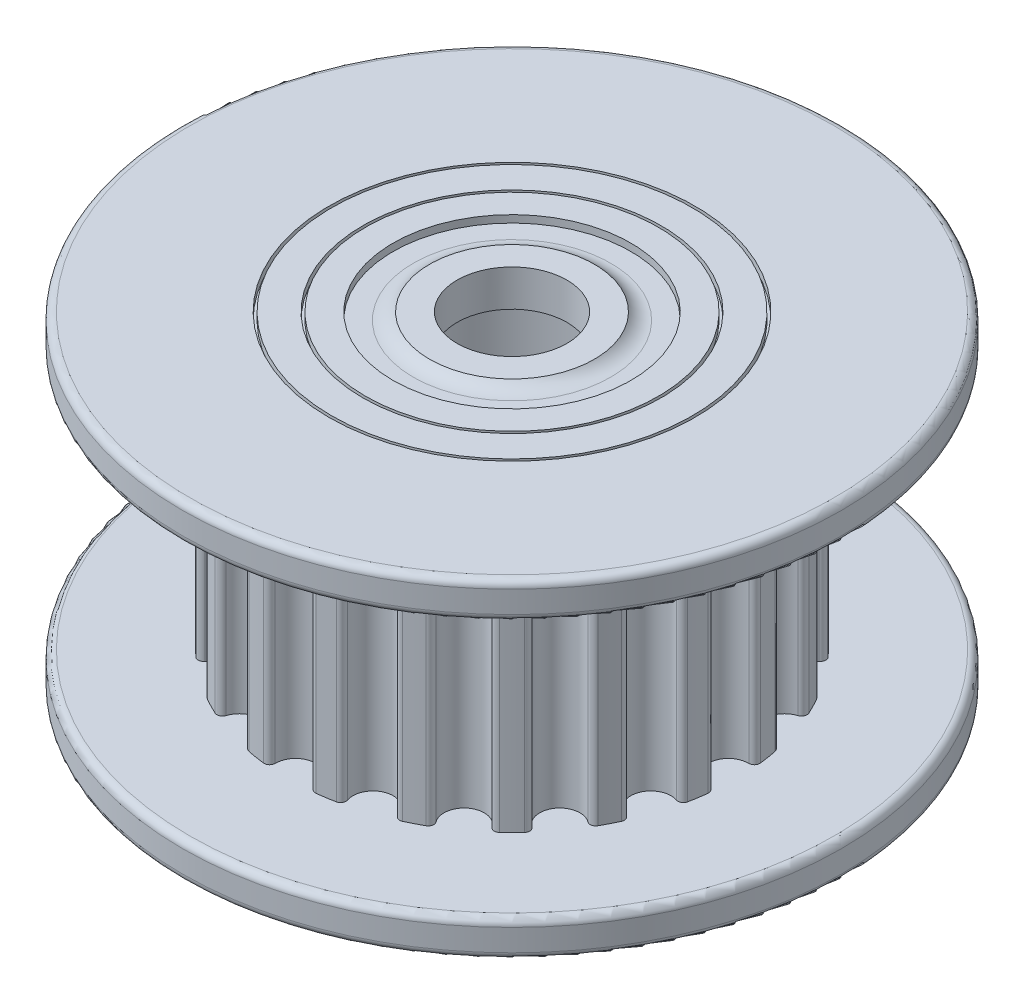
SolidWorks part; units mm, degrees
note: '?' marks a value the reader was unsure of.
material "1060 Alloy"
ref_plane "Спереди" through (0, 0, 0) normal (0, 0, 1) x (1, 0, 0)
ref_plane "Сверху" through (0, 0, 0) normal (0, 1, 0) x (1, 0, 0)
ref_plane "Справа" through (0, 0, 0) normal (1, 0, 0) x (0, 0, -1)
other "Configuration Table"
sketch "Эскиз1" plane through (0, 0, 0) normal (0, 1, 0) x (1, 0, 0)
  circle A0 centre (0, 0) radius 8
  circle A1 centre (0, 0) radius 2.5
  dimension "D1" = 16
  dimension "D2" = 5
extrude "Бобышка-Вытянуть1" add sketch "Эскиз1" along normal blind 7.45
sketch "Эскиз2" plane through (0, 7.45, 0) normal (0, 1, 0) x (1, 0, 0)
  arc A0 (-2.5575, 5.549) -> (-2.986, 5.3307) centre (0, 0) ccw
  circle A1 centre (0, 0) radius 2.5 construction
  circle A2 centre (0, 0) radius 2.5
  arc A3 (-0.55, 5.9169) -> (0.55, 5.9169) centre (0, 5.91) ccw
  arc A4 (1.3054, 5.7972) -> (2.3515, 5.4573) centre (1.8263, 5.6207) ccw
  arc A5 (3.0329, 5.1101) -> (3.9228, 4.4636) centre (3.4738, 4.7813) ccw
  arc A6 (4.4636, 3.9228) -> (5.1101, 3.0329) centre (4.7813, 3.4738) ccw
  arc A7 (5.4573, 2.3515) -> (5.7972, 1.3054) centre (5.6207, 1.8263) ccw
  arc A8 (5.9169, 0.55) -> (5.9169, -0.55) centre (5.91, 0) ccw
  arc A9 (5.7972, -1.3054) -> (5.4573, -2.3515) centre (5.6207, -1.8263) ccw
  arc A10 (5.1101, -3.0329) -> (4.4636, -3.9228) centre (4.7813, -3.4738) ccw
  arc A11 (3.9228, -4.4636) -> (3.0329, -5.1101) centre (3.4738, -4.7813) ccw
  arc A12 (2.3515, -5.4573) -> (1.3054, -5.7972) centre (1.8263, -5.6207) ccw
  arc A13 (0.55, -5.9169) -> (-0.55, -5.9169) centre (0, -5.91) ccw
  arc A14 (-1.3054, -5.7972) -> (-2.3515, -5.4573) centre (-1.8263, -5.6207) ccw
  arc A15 (-3.0329, -5.1101) -> (-3.9228, -4.4636) centre (-3.4738, -4.7813) ccw
  arc A16 (-4.4636, -3.9228) -> (-5.1101, -3.0329) centre (-4.7813, -3.4738) ccw
  arc A17 (-5.4573, -2.3515) -> (-5.7972, -1.3054) centre (-5.6207, -1.8263) ccw
  arc A18 (-5.9169, -0.55) -> (-5.9169, 0.55) centre (-5.91, 0) ccw
  arc A19 (-5.7972, 1.3054) -> (-5.4573, 2.3515) centre (-5.6207, 1.8263) ccw
  arc A20 (-5.1101, 3.0329) -> (-4.4636, 3.9228) centre (-4.7813, 3.4738) ccw
  arc A21 (-3.9228, 4.4636) -> (-3.0329, 5.1101) centre (-3.4738, 4.7813) ccw
  arc A22 (-2.3515, 5.4573) -> (-1.3054, 5.7972) centre (-1.8263, 5.6207) ccw
  arc A23 (-4.147, 4.4871) -> (-4.4871, 4.147) centre (0, 0) ccw
  arc A24 (-0.7176, 6.0677) -> (-1.1926, 5.9925) centre (0, 0) ccw
  arc A25 (1.1926, 5.9925) -> (0.7176, 6.0677) centre (0, 0) ccw
  arc A26 (2.986, 5.3307) -> (2.5575, 5.549) centre (0, 0) ccw
  arc A27 (4.4871, 4.147) -> (4.147, 4.4871) centre (0, 0) ccw
  arc A28 (5.549, 2.5575) -> (5.3307, 2.986) centre (0, 0) ccw
  arc A29 (6.0677, 0.7176) -> (5.9925, 1.1926) centre (0, 0) ccw
  arc A30 (-5.3307, 2.986) -> (-5.549, 2.5575) centre (0, 0) ccw
  arc A31 (-5.9925, 1.1926) -> (-6.0677, 0.7176) centre (0, 0) ccw
  arc A32 (-6.0677, -0.7176) -> (-5.9925, -1.1926) centre (0, 0) ccw
  arc A33 (-5.549, -2.5575) -> (-5.3307, -2.986) centre (0, 0) ccw
  arc A34 (-4.4871, -4.147) -> (-4.147, -4.4871) centre (0, 0) ccw
  arc A35 (-2.986, -5.3307) -> (-2.5575, -5.549) centre (0, 0) ccw
  arc A36 (5.9925, -1.1926) -> (6.0677, -0.7176) centre (0, 0) ccw
  arc A37 (5.3307, -2.986) -> (5.549, -2.5575) centre (0, 0) ccw
  arc A38 (4.147, -4.4871) -> (4.4871, -4.147) centre (0, 0) ccw
  arc A39 (2.5575, -5.549) -> (2.986, -5.3307) centre (0, 0) ccw
  arc A40 (0.7176, -6.0677) -> (1.1926, -5.9925) centre (0, 0) ccw
  arc A41 (-1.1926, -5.9925) -> (-0.7176, -6.0677) centre (0, 0) ccw
  arc A42 (5.9169, 0.55) -> (6.0677, 0.7176) centre (5.9188, 0.6999) ccw
  arc A43 (5.7972, 1.3054) -> (5.9925, 1.1926) centre (5.8454, 1.1633) cw
  arc A44 (5.4573, 2.3515) -> (5.549, 2.5575) centre (5.4128, 2.4947) ccw
  arc A45 (5.1101, 3.0329) -> (5.3307, 2.986) centre (5.1998, 2.9127) cw
  arc A46 (5.1101, -3.0329) -> (5.3307, -2.986) centre (5.1998, -2.9127) ccw
  arc A47 (5.4573, -2.3515) -> (5.549, -2.5575) centre (5.4128, -2.4947) cw
  arc A48 (5.7972, -1.3054) -> (5.9925, -1.1926) centre (5.8454, -1.1633) ccw
  arc A49 (5.9169, -0.55) -> (6.0677, -0.7176) centre (5.9188, -0.6999) cw
  arc A50 (3.9228, -4.4636) -> (4.147, -4.4871) centre (4.0452, -4.377) ccw
  arc A51 (4.4636, -3.9228) -> (4.4871, -4.147) centre (4.377, -4.0452) cw
  arc A52 (3.0329, -5.1101) -> (2.986, -5.3307) centre (2.9127, -5.1998) cw
  arc A53 (1.3054, -5.7972) -> (1.1926, -5.9925) centre (1.1633, -5.8454) cw
  arc A54 (0.55, -5.9169) -> (0.7176, -6.0677) centre (0.6999, -5.9188) ccw
  arc A55 (-0.55, -5.9169) -> (-0.7176, -6.0677) centre (-0.6999, -5.9188) cw
  arc A56 (-1.3054, -5.7972) -> (-1.1926, -5.9925) centre (-1.1633, -5.8454) ccw
  arc A57 (-2.3515, -5.4573) -> (-2.5575, -5.549) centre (-2.4947, -5.4128) cw
  arc A58 (-3.0329, -5.1101) -> (-2.986, -5.3307) centre (-2.9127, -5.1998) ccw
  arc A59 (-3.9228, -4.4636) -> (-4.147, -4.4871) centre (-4.0452, -4.377) cw
  arc A60 (-4.4636, -3.9228) -> (-4.4871, -4.147) centre (-4.377, -4.0452) ccw
  arc A61 (-5.9169, -0.55) -> (-6.0677, -0.7176) centre (-5.9188, -0.6999) ccw
  arc A62 (-5.7972, -1.3054) -> (-5.9925, -1.1926) centre (-5.8454, -1.1633) cw
  arc A63 (-5.4573, -2.3515) -> (-5.549, -2.5575) centre (-5.4128, -2.4947) ccw
  arc A64 (-5.1101, -3.0329) -> (-5.3307, -2.986) centre (-5.1998, -2.9127) cw
  arc A65 (-5.1101, 3.0329) -> (-5.3307, 2.986) centre (-5.1998, 2.9127) ccw
  arc A66 (-5.4573, 2.3515) -> (-5.549, 2.5575) centre (-5.4128, 2.4947) cw
  arc A67 (-5.7972, 1.3054) -> (-5.9925, 1.1926) centre (-5.8454, 1.1633) ccw
  arc A68 (-5.9169, 0.55) -> (-6.0677, 0.7176) centre (-5.9188, 0.6999) cw
  arc A69 (-4.4636, 3.9228) -> (-4.4871, 4.147) centre (-4.377, 4.0452) cw
  arc A70 (-3.9228, 4.4636) -> (-4.147, 4.4871) centre (-4.0452, 4.377) ccw
  arc A71 (-3.0329, 5.1101) -> (-2.986, 5.3307) centre (-2.9127, 5.1998) cw
  arc A72 (-2.3515, 5.4573) -> (-2.5575, 5.549) centre (-2.4947, 5.4128) ccw
  arc A73 (-1.3054, 5.7972) -> (-1.1926, 5.9925) centre (-1.1633, 5.8454) cw
  arc A74 (-0.55, 5.9169) -> (-0.7176, 6.0677) centre (-0.6999, 5.9188) ccw
  arc A75 (4.4636, 3.9228) -> (4.4871, 4.147) centre (4.377, 4.0452) ccw
  arc A76 (3.9228, 4.4636) -> (4.147, 4.4871) centre (4.0452, 4.377) cw
  arc A77 (0.55, 5.9169) -> (0.7176, 6.0677) centre (0.6999, 5.9188) cw
  arc A78 (1.3054, 5.7972) -> (1.1926, 5.9925) centre (1.1633, 5.8454) ccw
  arc A79 (3.0329, 5.1101) -> (2.986, 5.3307) centre (2.9127, 5.1998) ccw
  arc A80 (2.3515, 5.4573) -> (2.5575, 5.549) centre (2.4947, 5.4128) cw
  arc A81 (2.3515, -5.4573) -> (2.5575, -5.549) centre (2.4947, -5.4128) ccw
  point P69 (0, 0)
  point P135 (-0.5205, 6.0878)
  point P142 (0.5205, 6.0878)
  dimension "D1" = 12.22
  dimension "D2" = 1.1
  dimension "D3" = 0.75
  dimension "D5" = 0.15
  dimension "D6" = 0.15
  dimension "D4" = 20
extrude "Бобышка-Вытянуть2" add sketch "Эскиз2" along normal blind 7
sketch "Эскиз3" plane through (0, 14.45, 0) normal (0, 1, 0) x (1, 0, 0)
  circle A0 centre (0, 0) radius 2.5 construction
  circle A1 centre (0, 0) radius 2.5
  circle A2 centre (0, 0) radius 8 construction
  circle A3 centre (0, 0) radius 8
extrude "Бобышка-Вытянуть3" add sketch "Эскиз3" along normal blind 1.55
sketch "Эскиз4" plane through (0, 0, 0) normal (0, 0, 1) x (1, 0, 0)
  line L0 (-8, 3.725) -> (8, 3.725) construction
  line L1 (-8, 7.45) -> (-8, 0) construction
  line L2 (8, 0) -> (8, 7.45) construction
  circle A0 centre (0, 3.725) radius 1.25
  dimension "D1" = 2.5
extrude "Вырез-Вытянуть1" cut sketch "Эскиз4" along normal up to surface (7.9017 mm away)
sketch "Эскиз5" plane through (0, 0, 0) normal (1, 0, 0) x (0, 0, -1)
  line L0 (8, 3.725) -> (-7.9017, 3.725) construction
  line L1 (8, 0) -> (8, 7.45) construction
  circle A0 centre (0, 3.725) radius 1.25
  spline S1 degree 2 poles (-8, 4.975) (-7.8047, 3.725) (-8, 2.475) knots 0 0 0 1 1 1 weights 0.00675 0.008 0.00925 construction
  dimension "D1" = 2.5
extrude "Вырез-Вытянуть2" cut sketch "Эскиз5" along normal up to surface (7.9017 mm away)
sketch "Минимальный радиус ремня" plane through (0, 7.45, 0) normal (0, 1, 0) x (1, 0, 0)
  circle A0 centre (0, 0) radius 5.36
  arc A2 (-2.986, -5.3307) -> (-2.5575, -5.549) centre (0, 0) ccw construction
  dimension "D1" = 0.75
  dimension "D2" = 10.72
chamfer "Фаска1" distance 1 angle 30 2 edges at (0, 14.45, 8) (0, 7.45, 8)
ref_axis "Ось1" through (0, 16, 0) along (0, -1, 0)?
sketch "Sketch1" plane through (0, 16, 0) normal (0, 1, 0) x (1, 0, 0)
  circle A0 centre (0, 0) radius 8
  circle A1 centre (0, 0) radius 8 construction
extrude "Cut-Extrude1" cut sketch "Sketch1" against normal blind 0.75 and the other way through all
sketch "Sketch2" plane through (0, 14.45, 0) normal (0, -1, 0) x (1, 0, 0)
  circle A0 centre (0, 0) radius 9
  dimension "D1" = 18
extrude "Boss-Extrude1" add sketch "Sketch2" against normal blind 1
sketch "Sketch3" plane through (0, 0, 0) normal (0, -1, 0) x (1, 0, 0)
  circle A0 centre (0, 0) radius 8
  circle A1 centre (0, 0) radius 8 construction
extrude "Cut-Extrude2" cut sketch "Sketch3" against normal blind 7
sketch "Sketch4" plane through (0, 7.45, 0) normal (0, 1, 0) x (1, 0, 0)
  circle A0 centre (0, 0) radius 9
  circle A1 centre (0, 0) radius 9 construction
extrude "Boss-Extrude2" add sketch "Sketch4" against normal blind 1
sketch "Sketch5" plane through (0, 15.45, 0) normal (0, 1, 0) x (1, 0, 0)
  circle A0 centre (0, 0) radius 5
  dimension "D1" = 10
extrude "Cut-Extrude4" cut sketch "Sketch5" against normal blind 0.2
sketch "Sketch7" plane through (0, 6.45, 0) normal (0, -1, 0) x (1, 0, 0)
  circle A0 centre (0, 0) radius 5
  dimension "D1" = 10
extrude "Cut-Extrude5" cut sketch "Sketch7" against normal blind 0.2
sketch "Sketch8" plane through (0, 6.65, 0) normal (0, -1, 0) x (1, 0, 0)
  circle A0 centre (0, 0) radius 4.075
  circle A1 centre (0, 0) radius 4.925
  dimension "D1" = 8.15
  dimension "D2" = 9.85
extrude "Boss-Extrude3" add sketch "Sketch8" along normal blind 0.2
sketch "Sketch9" plane through (0, 15.25, 0) normal (0, 1, 0) x (1, 0, 0)
  circle A0 centre (0, 0) radius 4.075
  circle A1 centre (0, 0) radius 4.925
  dimension "D1" = 8.15
  dimension "D2" = 9.85
extrude "Boss-Extrude4" add sketch "Sketch9" along normal blind 0.2
sketch "Sketch12" plane through (0, 15.25, 0) normal (0, 1, 0) x (1, 0, 0)
  circle A0 centre (0, 0) radius 4
  circle A1 centre (0, 0) radius 3.25
  dimension "D1" = 8
  dimension "D2" = 6.5
extrude "Boss-Extrude5" add sketch "Sketch12" along normal blind 0.2
sketch "Sketch13" plane through (0, 6.65, 0) normal (0, -1, 0) x (1, 0, 0)
  circle A0 centre (0, 0) radius 4
  circle A1 centre (0, 0) radius 3.25
  dimension "D1" = 8
  dimension "D2" = 6.5
extrude "Boss-Extrude6" add sketch "Sketch13" along normal blind 0.2
sketch "Sketch14" plane through (0, 15.25, 0) normal (0, 1, 0) x (1, 0, 0)
  circle A0 centre (0, 0) radius 2.25
  circle A1 centre (0, 0) radius 1.5
  dimension "D1" = 4.5
  dimension "D2" = 3
extrude "Boss-Extrude7" add sketch "Sketch14" along normal blind 0.2
sketch "Sketch15" plane through (0, 6.65, 0) normal (0, -1, 0) x (1, 0, 0)
  circle A0 centre (0, 0) radius 2.25
  circle A1 centre (0, 0) radius 1.5
  dimension "D1" = 4.5
  dimension "D2" = 3
extrude "Boss-Extrude8" add sketch "Sketch15" along normal blind 0.2
sketch "Sketch16" plane through (0, 15.25, 0) normal (0, 1, 0) x (1, 0, 0)
  circle A0 centre (0, 0) radius 1.5
  circle A1 centre (0, 0) radius 1.5 construction
extrude "Cut-Extrude6" cut sketch "Sketch16" against normal blind 10.2
fillet "Fillet1" radius 0.6 2 edges at (0, 6.65, -2.25) (0, 15.25, 2.25)
fillet "Fillet2" radius 0.2 4 edges at (0, 15.45, -9) (0, 14.45, -9) (0, 7.45, 9) (0, 6.45, 9)
